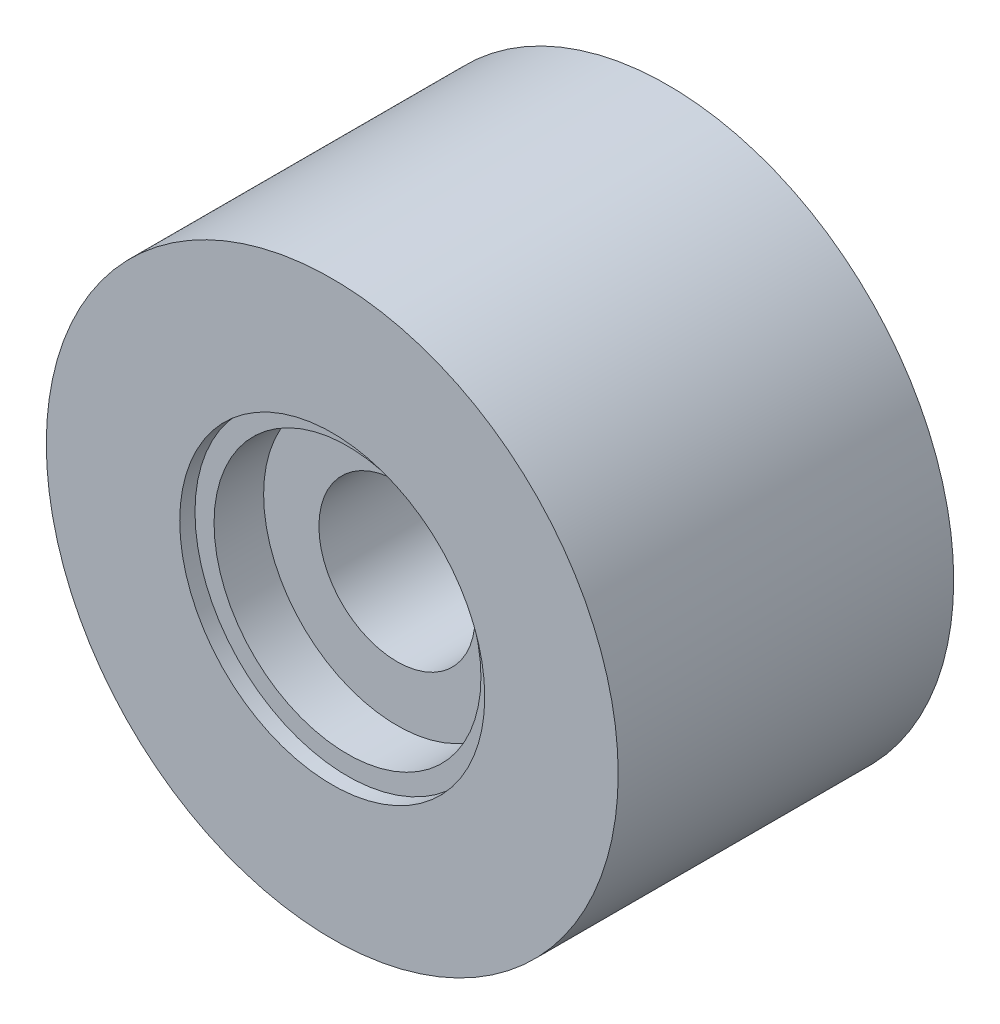
SolidWorks part; units mm, degrees
ref_plane "前视基准面" through (0, 0, 0) normal (0, 0, 1) x (1, 0, 0)
ref_plane "上视基准面" through (0, 0, 0) normal (0, 1, 0) x (1, 0, 0)
ref_plane "右视基准面" through (0, 0, 0) normal (1, 0, 0) x (0, 0, -1)
sketch "草图1" plane through (0, 0, 0) normal (0, 0, 1) x (1, 0, 0)
  circle A0 centre (0, 0) radius 7
  circle A1 centre (0, 0) radius 15
extrude "凸台-拉伸1" add sketch "草图1" along normal blind 2.6
sketch "草图2" plane through (0, 0, 2.6) normal (0, 0, 1) x (1, 0, 0)
  circle A0 centre (0, 0) radius 4
  circle A1 centre (0, 0) radius 15
extrude "凸台-拉伸2" add sketch "草图2" along normal blind 10.8
sketch "草图3" plane through (0, 0, 13.4) normal (0, 0, 1) x (1, 0, 0)
  circle A0 centre (0, 0) radius 7
  circle A1 centre (0, 0) radius 15
extrude "凸台-拉伸3" add sketch "草图3" along normal blind 2.6
sketch "草图4" plane through (0, 0, 0) normal (0, 0, -1) x (-1, 0, 0)
  circle A0 centre (0, 0) radius 8
  circle A1 centre (0, 0) radius 15
extrude "凸台-拉伸4" add sketch "草图4" along normal blind 0.8
sketch "草图5" plane through (0, 0, 16) normal (0, 0, 1) x (1, 0, 0)
  circle A0 centre (0, 0) radius 8
  circle A1 centre (0, 0) radius 15
extrude "凸台-拉伸5" add sketch "草图5" along normal blind 0.8
sketch "草图6" plane through (0, 0, 2.6) normal (0, 0, -1) x (-1, 0, 0)
  circle A0 centre (0, 0) radius 4.1
extrude "切除-拉伸1" cut sketch "草图6" against normal blind 30
